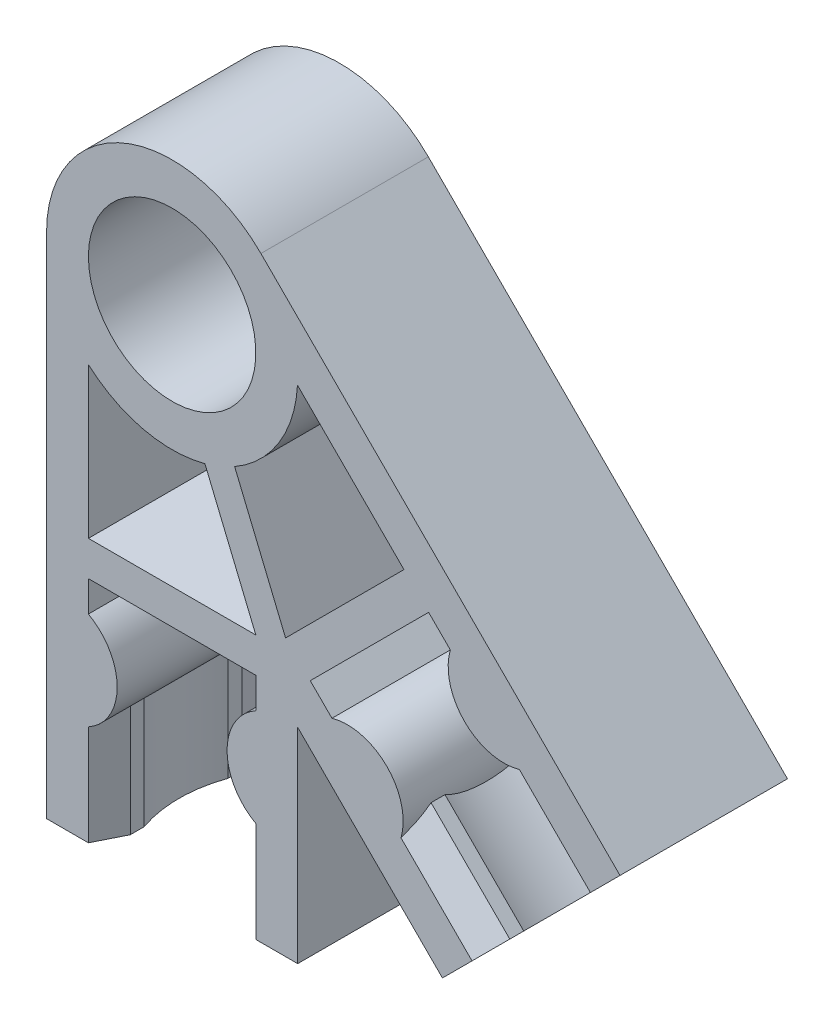
SolidWorks part; units mm, degrees
ref_plane "前视基准面" through (0, 0, 0) normal (0, 0, 1) x (1, 0, 0)
ref_plane "上视基准面" through (0, 0, 0) normal (0, 1, 0) x (1, 0, 0)
ref_plane "右视基准面" through (0, 0, 0) normal (1, 0, 0) x (0, 0, -1)
sketch "草图1" plane through (0, 0, 0) normal (0, 0, 1) x (1, 0, 0)
  line L0 (-4.5, 0) -> (-4.5, -18.2)
  line L1 (4.5, 0) -> (4.5, -18.2)
  line L2 (-4.5, -18.2) -> (-3, -18.2)
  line L3 (-3, -18.2) -> (-3, -14.6)
  line L4 (4.5, -18.2) -> (3, -18.2)
  line L5 (3, -18.2) -> (3, -14.6)
  line L6 (-3, -11.1) -> (-3, -10)
  line L7 (-3, -10) -> (3, -10)
  line L8 (3, -10) -> (3, -11.1)
  arc A0 (4.5, 0) -> (-4.5, 0) centre (0, 0) ccw
  arc A1 (-3, -11.1) -> (-3, -14.6) centre (-3.9682, -12.85) cw
  arc A2 (3, -11.1) -> (3, -14.6) centre (3.9682, -12.85) ccw
  point P1 (0, 4.5)
  dimension "D1" = 9
  dimension "D10" = 14.5
  dimension "D11" = 2
  dimension "D12" = 2
  dimension "D2" = 18.2
  dimension "D3" = 18.2
  dimension "D4" = 1.5
  dimension "D5" = 1.5
  dimension "D6" = 1.1
  dimension "D7" = 1.1
  dimension "D8" = 3.5
  dimension "D9" = 3.5
extrude "凸台-拉伸1" add sketch "草图1" along normal blind 6
sketch "草图3" plane through (0, -18.2, 0) normal (0, -1, 0) x (1, 0, 0)
  line L0 (-3, 6) -> (-3, 0)
  line L1 (-3, 0) -> (-2.5, 1)
  line L2 (-2.5, 1) -> (-2.5, 1.5)
  line L3 (-3, 6) -> (-2.5, 5)
  line L4 (-2.5, 5) -> (-2.5, 4.5)
  line L5 (0, 0) -> (0, 6.4845) construction
  line L6 (3, 0) -> (2.5, 1)
  line L7 (2.5, 1) -> (2.5, 1.5)
  line L8 (2.5, 5) -> (2.5, 4.5)
  line L9 (3, 6) -> (2.5, 5)
  line L10 (3, 6) -> (3, 0)
  arc A0 (-2.5, 1.5) -> (-2.5, 4.5) centre (1.7426, 3) cw
  arc A1 (2.5, 1.5) -> (2.5, 4.5) centre (-1.7426, 3) ccw
  dimension "D7" = 4.5
  dimension "D1" = 0.5
  dimension "D2" = 0.5
  dimension "D3" = 0.5
  dimension "D4" = 0.5
  dimension "D5" = 1.5
  dimension "D6" = 1.5
extrude "凸台-拉伸2" add sketch "草图3" against normal up to next
ref_axis "Axis" through (0, 0, 0) along (0, 0, 1)
pattern_circular "阵列(圆周)1" count 2 every 45 about axis through (0, 0, 0) along (0, 0, 1) of "凸台-拉伸1", "凸台-拉伸2"
sketch "草图4" plane through (0, 0, 0) normal (0, 0, -1) x (-1, 0, 0)
  line L0 (3, -8.75) -> (3, -3.3541)
  line L1 (-3, -8.75) -> (-1.1749, -4.3439)
  line L2 (3, -8.75) -> (-3, -8.75)
  line L3 (3, -10) -> (-3, -10) construction
  line L4 (-8.3085, -4.0659) -> (-4.493, -0.2504)
  line L5 (0, 0) -> (-4.5, -10.864) construction
  line L6 (-8.3085, -4.0659) -> (-4.0659, -8.3085)
  line L7 (-4.0659, -8.3085) -> (-2.2408, -3.9024)
  circle A0 centre (0, 0) radius 3
  arc A1 (-4.493, -0.2504) -> (-2.2408, -3.9024) centre (0, 0) ccw
  arc A2 (-1.1749, -4.3439) -> (3, -3.3541) centre (0, 0) ccw
  dimension "D1" = 9
  dimension "D2" = 6
  dimension "D3" = 1.25
  dimension "D4" = 6
extrude "切除-拉伸2" cut sketch "草图4" against normal through all
